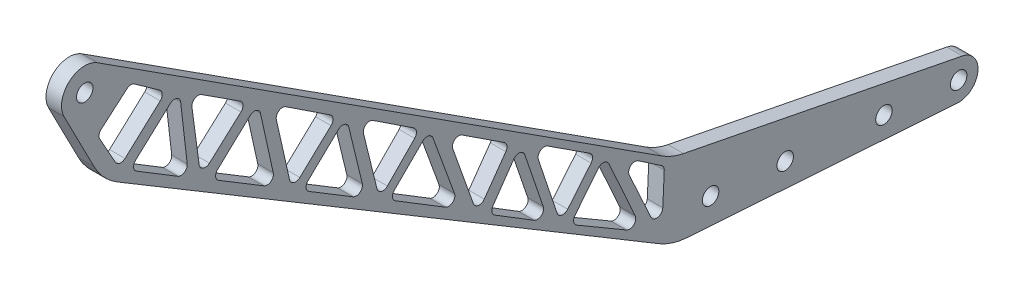
SolidWorks part; units mm, degrees
ref_plane "Front Plane" through (0, 0, 0) normal (0, 0, 1) x (1, 0, 0)
ref_plane "Top Plane" through (0, 0, 0) normal (0, 1, 0) x (1, 0, 0)
ref_plane "Right Plane" through (0, 0, 0) normal (1, 0, 0) x (0, 0, -1)
ref_plane "Plane1" through (-76.9133, 0, 0) normal (1, 0, 0) x (0, 0, -1)
sketch "Sketch1" plane through (-76.9133, 0, 0) normal (1, 0, 0) x (0, 0, -1)
  line L0 (535.7661, 896.8306) -> (535.7661, 915.8806) construction
  line L1 (434.1661, 906.5188) -> (434.1661, 925.5688) construction
  line L2 (177.8, 1090.4307) -> (434.1661, 925.5688) construction
  line L3 (139.7, 1090.4307) -> (177.8, 1090.4307) construction
  line L4 (535.7661, 896.8306) -> (535.7661, 915.8806) construction
  line L5 (434.1661, 906.5188) -> (434.1661, 925.5688) construction
  line L6 (177.8, 1090.4307) -> (434.1661, 925.5688) construction
  line L7 (139.7, 1090.4307) -> (177.8, 1090.4307) construction
  line L8 (535.2188, 907.962) -> (418.2911, 916.0438)
  line L9 (537.2996, 923.6685) -> (418.2911, 947.1021)
  line L10 (169.3326, 1086.0686) -> (184.9514, 1055.7506)
  line L11 (184.9514, 1055.7506) -> (418.2911, 916.0438)
  line L12 (418.2911, 947.1021) -> (182.9519, 1098.4422)
  line L13 (434.1661, 925.5688) -> (535.7661, 915.8806) construction
  circle A0 centre (177.8, 1090.4307) radius 3.3782
  circle A1 centre (434.1661, 925.5688) radius 3.3782
  circle A2 centre (535.7661, 915.8806) radius 3.3782
  arc A3 (535.2188, 907.962) -> (537.2996, 923.6685) centre (535.7661, 915.8806) ccw
  arc A5 (182.9519, 1098.4422) -> (169.3326, 1086.0686) centre (177.8, 1090.4307) ccw
  arc A6 (537.2996, 923.6685) -> (535.2188, 907.962) centre (535.7661, 915.8806) ccw construction
  arc A7 (169.3326, 1086.0686) -> (185.8114, 1085.2788) centre (177.8, 1090.4307) ccw construction
  arc A8 (185.8114, 1085.2788) -> (182.9519, 1098.4422) centre (177.8, 1090.4307) ccw construction
  circle A9 centre (464.7144, 922.6558) radius 3.3782
  circle A10 centre (505.1709, 918.798) radius 3.3782
  spline S0 degree 3 poles (935.6767, 939.7163) (940.3147, 942.1548) (935.2529, 940.0507) (930.9716, 938.764) (920.6916, 935.461) (907.9553, 931.9087) (891.2949, 927.4743) (871.5218, 922.6042) (848.5739, 917.4165) (822.7695, 912.1503) (794.3904, 907.0475) (763.8436, 902.4482) (731.6326, 898.5836) (698.2942, 895.5048) (664.3294, 893.3038) (630.2914, 892.1587) (596.9177, 892.4579) (565.0805, 894.155) (535.5455, 896.7257) (508.8897, 899.7641) (485.4664, 902.8148) (465.3261, 905.1664) (448.3721, 906.4646) (434.4368, 906.7165) (423.4463, 905.9074) (416.5733, 904.5379) (412.9407, 903.1204) (411.5732, 902.4729) (410.4746, 901.8174) (409.7947, 901.3358) (409.3397, 900.9203) (409.0422, 900.6195) (408.7846, 900.3039) (408.5873, 899.9553) (408.4178, 899.5844) (408.2374, 899.0451) (408.051, 898.3239) (407.9116, 897.2265) (407.8599, 894.9991) (408.6865, 890.8402) (411.376, 884.946) (416.2539, 878.2548) (423.1327, 871.4111) (431.9816, 864.5947) (442.7539, 857.9825) (455.382, 851.7275) (469.765, 845.9615) (485.7865, 840.8065) (503.3041, 836.37) (522.1586, 832.7575) (542.1676, 830.0521) (563.1459, 828.3505) (584.9266, 827.7965) (607.3492, 828.4639) (630.2782, 830.4035) (653.5854, 833.657) (677.1845, 838.2437) (700.9897, 844.1113) (724.9284, 850.9153) (748.8232, 858.3979) (772.4019, 866.3681) (795.3921, 874.6046) (817.5075, 882.9123) (838.4515, 891.1278) (857.9391, 899.0809) (875.6775, 906.6433) (891.4161, 913.7156) (904.9213, 920.2497) (916.21, 926.5709) (924.8872, 932.3286) (932.3848, 937.3638) (935.6767, 939.7163) (940.3147, 942.1548) (935.2529, 940.0507) knots -0.014576 -0.006911 -0.001813 0 0.001841 0.007308 0.016237 0.028456 0.043801 0.062126 0.08324 0.106896 0.132817 0.160613 0.189791 0.219873 0.250457 0.281127 0.311257 0.339999 0.366671 0.390812 0.411995 0.430069 0.445224 0.457619 0.467425 0.474786 0.47628 0.477884 0.47884 0.479711 0.480113 0.480492 0.480846 0.481203 0.481564 0.48194 0.482727 0.483559 0.484903 0.488692 0.494806 0.502149 0.510796 0.520764 0.532062 0.544666 0.558541 0.573612 0.589803 0.60701 0.625107 0.643967 0.663469 0.683551 0.704142 0.725196 0.74668 0.768633 0.790977 0.813463 0.835827 0.857772 0.879003 0.899228 0.918151 0.935487 0.950987 0.964428 0.975828 0.985424 0.993089 0.998187 1 1.001841 1.007308 1.016237 only from (939.324, 941.6889) to (939.324, 941.6889) construction
  spline S1 degree 3 poles (935.6767, 939.7163) (940.3147, 942.1548) (935.2529, 940.0507) (930.9716, 938.764) (920.6916, 935.461) (907.9553, 931.9087) (891.2949, 927.4743) (871.5218, 922.6042) (848.5739, 917.4165) (822.7695, 912.1503) (794.3904, 907.0475) (763.8436, 902.4482) (731.6326, 898.5836) (698.2942, 895.5048) (664.3294, 893.3038) (630.2914, 892.1587) (596.9177, 892.4579) (565.0805, 894.155) (535.5455, 896.7257) (508.8897, 899.7641) (485.4664, 902.8148) (465.3261, 905.1664) (448.3721, 906.4646) (434.4368, 906.7165) (423.4463, 905.9074) (416.5733, 904.5379) (412.9407, 903.1204) (411.5732, 902.4729) (410.4746, 901.8174) (409.7947, 901.3358) (409.3397, 900.9203) (409.0422, 900.6195) (408.7846, 900.3039) (408.5873, 899.9553) (408.4178, 899.5844) (408.2374, 899.0451) (408.051, 898.3239) (407.9116, 897.2265) (407.8599, 894.9991) (408.6865, 890.8402) (411.376, 884.946) (416.2539, 878.2548) (423.1327, 871.4111) (431.9816, 864.5947) (442.7539, 857.9825) (455.382, 851.7275) (469.765, 845.9615) (485.7865, 840.8065) (503.3041, 836.37) (522.1586, 832.7575) (542.1676, 830.0521) (563.1459, 828.3505) (584.9266, 827.7965) (607.3492, 828.4639) (630.2782, 830.4035) (653.5854, 833.657) (677.1845, 838.2437) (700.9897, 844.1113) (724.9284, 850.9153) (748.8232, 858.3979) (772.4019, 866.3681) (795.3921, 874.6046) (817.5075, 882.9123) (838.4515, 891.1278) (857.9391, 899.0809) (875.6775, 906.6433) (891.4161, 913.7156) (904.9213, 920.2497) (916.21, 926.5709) (924.8872, 932.3286) (932.3848, 937.3638) (935.6767, 939.7163) (940.3147, 942.1548) (935.2529, 940.0507) knots -0.014576 -0.006911 -0.001813 0 0.001841 0.007308 0.016237 0.028456 0.043801 0.062126 0.08324 0.106896 0.132817 0.160613 0.189791 0.219873 0.250457 0.281127 0.311257 0.339999 0.366671 0.390812 0.411995 0.430069 0.445224 0.457619 0.467425 0.474786 0.47628 0.477884 0.47884 0.479711 0.480113 0.480492 0.480846 0.481203 0.481564 0.48194 0.482727 0.483559 0.484903 0.488692 0.494806 0.502149 0.510796 0.520764 0.532062 0.544666 0.558541 0.573612 0.589803 0.60701 0.625107 0.643967 0.663469 0.683551 0.704142 0.725196 0.74668 0.768633 0.790977 0.813463 0.835827 0.857772 0.879003 0.899228 0.918151 0.935487 0.950987 0.964428 0.975828 0.985424 0.993089 0.998187 1 1.001841 1.007308 1.016237 only from (939.324, 941.6889) to (939.324, 941.6889) construction
  dimension "D1" = 6.7564
  dimension "D2" = 6.7564
  dimension "D3" = 6.7564
  dimension "D4" = 15.875
  dimension "D5" = 30
  dimension "D6" = 19.05
  dimension "D10" = 6.7564
  dimension "D11" = 6.7564
  dimension "D7" = 148.166
  dimension "D8" = 15.875
  dimension "D9" = 9.525
  dimension "D12" = 40.64
  dimension "D13" = 30.734
extrude "Boss-Extrude1" add sketch "Sketch1" along normal mid plane 6.35
fillet "Fillet1" radius 25.4 3 edges at (-76.9133, 1055.7506, -184.9514) (-76.9133, 947.1021, -418.2911) (-76.9133, 916.0438, -418.2911)
sketch "Sketch2" plane through (-73.7383, 0, 0) normal (1, 0, 0) x (0, 0, -1)
  line L6 (212.8295, 1069.041) -> (198.606, 1055.9934)
  line L7 (217.0697, 1067.4611) -> (219.7682, 1044.1331)
  line L8 (215.9263, 1041.6704) -> (199.0043, 1051.9508)
  line L9 (221.7077, 1063.3434) -> (224.6501, 1041.3976)
  line L10 (228.8738, 1039.8536) -> (241.7874, 1051.5641)
  line L11 (241.4587, 1055.5797) -> (225.6027, 1065.815)
  line L12 (249.7605, 1047.1075) -> (255.0131, 1023.357)
  line L13 (251.218, 1020.6354) -> (232.6267, 1031.8852)
  line L14 (232.2048, 1035.9116) -> (245.5435, 1048.4123)
  line L15 (256.2887, 1041.5496) -> (261.6992, 1017.5322)
  line L16 (265.9184, 1016.2413) -> (278.6819, 1028.2603)
  line L17 (278.34, 1032.2292) -> (260.166, 1044.2275)
  line L18 (285.9508, 1024.1277) -> (291.4891, 1001.274)
  line L19 (287.7049, 998.503) -> (269.6883, 1009.4129)
  line L20 (269.2476, 1013.4205) -> (281.7259, 1025.3644)
  line L21 (291.9877, 1018.7934) -> (297.5035, 996.4443)
  line L22 (301.7822, 995.2737) -> (312.9339, 1006.6348)
  line L23 (312.5193, 1010.5347) -> (295.8517, 1021.5227)
  line L24 (320.4317, 1003.0426) -> (329.2353, 978.9361)
  line L25 (325.5244, 975.8978) -> (305.073, 988.4025)
  line L26 (304.6055, 992.3691) -> (316.2534, 1003.9709)
  line L27 (328.5613, 995.1219) -> (337.0009, 971.414)
  line L28 (341.465, 970.7956) -> (350.2883, 983.2249)
  line L29 (349.6064, 986.8216) -> (332.3434, 998.1001)
  line L30 (358.0244, 978.3225) -> (365.6133, 956.0674)
  line L31 (361.8794, 953.0835) -> (345.7383, 963.0022)
  line L32 (344.9806, 966.6134) -> (353.5329, 978.9499)
  line L33 (363.6159, 973.7211) -> (371.269, 950.9287)
  line L34 (375.6344, 950.1187) -> (385.2284, 961.7217)
  line L35 (384.6533, 965.4711) -> (367.4062, 976.6604)
  line L36 (388.1861, 958.4199) -> (378.5999, 946.4446)
  line L37 (379.3, 942.665) -> (399.6766, 930.7417)
  line L38 (403.2744, 933.9792) -> (392.484, 957.8779)
  line L39 (400.8201, 949.6856) -> (409.729, 930.2453)
  line L40 (414.5753, 931.1847) -> (415.1835, 944.1767)
  line L41 (414.071, 946.3983) -> (404.5539, 952.8466)
  line L42 (208.7115, 1072.0152) -> (194.2879, 1058.8022)
  line L43 (190.3558, 1059.4345) -> (183.9642, 1070.8533)
  line L44 (184.5202, 1074.0161) -> (195.0647, 1083.1245)
  line L45 (198.1985, 1083.2713) -> (208.4691, 1075.9571)
  arc A0 (194.2879, 1058.8022) -> (190.3558, 1059.4345) centre (192.5722, 1060.6752) cw
  arc A1 (208.7115, 1072.0152) -> (208.4691, 1075.9571) centre (206.9957, 1073.8881) ccw
  arc A2 (415.1835, 944.1767) -> (414.071, 946.3983) centre (412.6462, 944.2955) ccw
  arc A3 (400.8201, 949.6856) -> (404.5539, 952.8466) centre (403.1292, 950.7438) cw
  arc A4 (409.729, 930.2453) -> (414.5753, 931.1847) centre (412.038, 931.3034) ccw
  arc A5 (399.6766, 930.7417) -> (403.2744, 933.9792) centre (400.9594, 932.934) ccw
  arc A6 (378.5999, 946.4446) -> (379.3, 942.665) centre (380.5828, 944.8573) ccw
  arc A7 (388.1861, 958.4199) -> (392.484, 957.8779) centre (390.169, 956.8326) cw
  arc A8 (385.2284, 961.7217) -> (384.6533, 965.4711) centre (383.2709, 963.3403) ccw
  arc A9 (363.6159, 973.7211) -> (367.4062, 976.6604) centre (366.0238, 974.5296) cw
  arc A10 (371.269, 950.9287) -> (375.6344, 950.1187) centre (373.6769, 951.7373) ccw
  arc A11 (365.6133, 956.0674) -> (361.8794, 953.0835) centre (363.2092, 955.2476) cw
  arc A12 (345.7383, 963.0022) -> (344.9806, 966.6134) centre (347.0681, 965.1663) cw
  arc A13 (358.0244, 978.3225) -> (353.5329, 978.9499) centre (355.6204, 977.5028) ccw
  arc A14 (328.5613, 995.1219) -> (332.3434, 998.1001) centre (330.9542, 995.9737) cw
  arc A15 (350.2883, 983.2249) -> (349.6064, 986.8216) centre (348.2171, 984.6952) ccw
  arc A16 (341.465, 970.7956) -> (337.0009, 971.414) centre (339.3938, 972.2659) cw
  arc A17 (329.2353, 978.9361) -> (325.5244, 975.8978) centre (326.8494, 978.0648) cw
  arc A18 (320.4317, 1003.0426) -> (316.2534, 1003.9709) centre (318.0459, 1002.1713) ccw
  arc A19 (305.073, 988.4025) -> (304.6055, 992.3691) centre (306.398, 990.5695) cw
  arc A20 (297.5035, 996.4443) -> (301.7822, 995.2737) centre (299.9695, 997.0529) ccw
  arc A21 (312.9339, 1006.6348) -> (312.5193, 1010.5347) centre (311.1213, 1008.4141) ccw
  arc A22 (291.9877, 1018.7934) -> (295.8517, 1021.5227) centre (294.4537, 1019.4021) cw
  arc A23 (291.4891, 1001.274) -> (287.7049, 998.503) centre (289.0205, 1000.6757) cw
  arc A24 (269.6883, 1009.4129) -> (269.2476, 1013.4205) centre (271.0039, 1011.5856) cw
  arc A25 (285.9508, 1024.1277) -> (281.7259, 1025.3644) centre (283.4822, 1023.5295) ccw
  arc A26 (256.2887, 1041.5496) -> (260.166, 1044.2275) centre (258.7666, 1042.1078) cw
  arc A27 (278.6819, 1028.2603) -> (278.34, 1032.2292) centre (276.9406, 1030.1094) ccw
  arc A28 (265.9184, 1016.2413) -> (261.6992, 1017.5322) centre (264.1771, 1018.0904) cw
  arc A29 (255.0131, 1023.357) -> (251.218, 1020.6354) centre (252.533, 1022.8085) cw
  arc A30 (232.6267, 1031.8852) -> (232.2048, 1035.9116) centre (233.9417, 1034.0583) cw
  arc A31 (249.7605, 1047.1075) -> (245.5435, 1048.4123) centre (247.2804, 1046.559) ccw
  arc A32 (221.7077, 1063.3434) -> (225.6027, 1065.815) centre (224.2251, 1063.6809) cw
  arc A33 (241.7874, 1051.5641) -> (241.4587, 1055.5797) centre (240.0812, 1053.4457) ccw
  arc A34 (224.6501, 1041.3976) -> (228.8738, 1039.8536) centre (227.1675, 1041.7351) ccw
  arc A35 (219.7682, 1044.1331) -> (215.9263, 1041.6704) centre (217.2451, 1043.8412) cw
  arc A36 (212.8295, 1069.041) -> (217.0697, 1067.4611) centre (214.5465, 1067.1693) cw
  arc A37 (198.606, 1055.9934) -> (199.0043, 1051.9508) centre (200.3231, 1054.1216) ccw
  arc A38 (183.9642, 1070.8533) -> (184.5202, 1074.0161) centre (186.1806, 1072.0939) cw
  arc A39 (195.0647, 1083.1245) -> (198.1985, 1083.2713) centre (196.7251, 1081.2023) cw
  point P2 (196.1587, 1083.6865)
  point P5 (182.9521, 1072.6615)
  point P6 (191.0089, 1057.6756)
  point P7 (211.0265, 1074.1359)
  point P8 (191.9226, 1056.6354)
  point P9 (196.574, 1084.4282)
  dimension "D1" = 2.54
  dimension "D2" = 2.54
extrude "Cut-Extrude3" cut sketch "Sketch2" against normal through all
